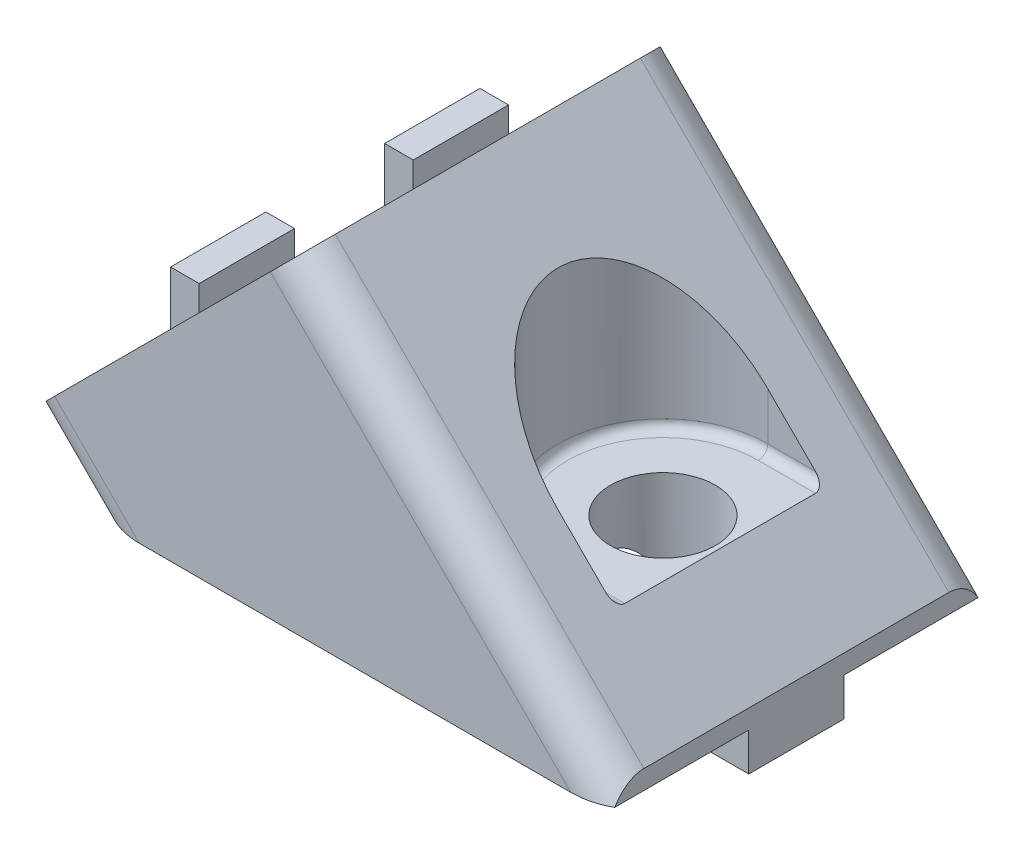
SolidWorks part; units mm, degrees
ref_plane "Front Plane" through (0, 0, 0) normal (0, 0, 1) x (1, 0, 0)
ref_plane "Top Plane" through (0, 0, 0) normal (0, 1, 0) x (1, 0, 0)
ref_plane "Right Plane" through (0, 0, 0) normal (1, 0, 0) x (0, 0, -1)
sketch "Sketch1" plane through (0, 0, 0) normal (0, 0, 1) x (1, 0, 0)
  line L0 (0, 0) -> (-3.0406, 3.0406)
  line L1 (27.2843, 1) -> (11.1016, 17.1827)
  line L2 (27.2843, 0) -> (27.2843, 1)
  line L3 (27.2843, 1) -> (28.2843, 0) construction
  line L4 (11.1016, 17.1827) -> (-3.0406, 3.0406)
  line L5 (27.2843, 0) -> (0, 0)
  line L6 (27.2843, 0) -> (28.2843, 0) construction
  dimension "D1" = 45
  dimension "D2" = 20
  dimension "D3" = 24.3
  dimension "D4" = 1
extrude "Boss-Extrude1" add sketch "Sketch1" along normal mid plane 20
sketch "Sketch2" plane through (0, 0, 0) normal (0, 1, 0) x (1, 0, 0)
  line L0 (28.2843, 0) -> (20.2843, 0) construction
  line L2 (28.2843, -10) -> (28.2843, 10) construction
  circle A0 centre (20.2843, 0) radius 2.75
  circle A1 centre (20.2843, 0) radius 5.5 construction
  dimension "D2" = 5.5
  dimension "D3" = 11
  dimension "D1" = 8
extrude "Cut-Extrude1" cut sketch "Sketch2" against normal through all from offset 5
sketch "Sketch3" plane through (0, 5, 0) normal (0, -1, 0) x (1, 0, 0)
  line L0 (20.2843, -5.5) -> (28.2843, -5.5)
  line L2 (20.2843, 5.5) -> (28.2843, 5.5)
  line L3 (28.2843, 5.5) -> (28.2843, -5.5)
  arc A0 (20.2843, 5.5) -> (20.2843, -5.5) centre (20.2843, 0) ccw
  circle A1 centre (20.2843, 0) radius 5.5 construction
extrude "Cut-Extrude2" cut sketch "Sketch3" against normal through all
fillet "Fillet1" radius 2 4 edges at (-1.5203, 1.5203, -10) (-1.5203, 1.5203, 10) (19.1929, 9.0913, -10) (19.1929, 9.0913, 10)
fillet "Fillet2" radius 0.5 3 edges at (21.7843, 5, 5.5) (21.7843, 5, -5.5) (14.7843, 5, 0)
sketch "Sketch4" plane through (0, 0, 0) normal (0, 0, 1) x (1, 0, 0)
  line L0 (27.2843, 0) -> (0, 0) construction
  line L1 (7.5, 0) -> (0, 0)
  line L2 (7.5, 0) -> (7.5, -2)
  line L3 (7.5, -2) -> (0, -2)
  line L4 (0, 0) -> (0, -2)
  line L5 (11.1016, 17.1827) -> (-3.0406, 3.0406) construction
  line L6 (24.2843, 0) -> (27.2843, 0)
  line L7 (24.2843, 0) -> (24.2843, -2)
  line L8 (24.2843, -2) -> (27.2843, -2)
  line L9 (27.2843, 0) -> (27.2843, -2)
  line L10 (-3.0406, 5.869) -> (-1.5406, 5.869)
  line L11 (-3.0406, 5.869) -> (-3.0406, 3.0406)
  line L12 (-3.0406, 3.0406) -> (-1.5406, 4.5406)
  line L13 (-1.5406, 5.869) -> (-1.5406, 4.5406)
  line L14 (8.1874, 17.0969) -> (9.6874, 17.0969)
  line L15 (8.1874, 17.0969) -> (8.1874, 14.2685)
  line L16 (8.1874, 14.2685) -> (9.6874, 15.7685)
  line L17 (9.6874, 17.0969) -> (9.6874, 15.7685)
  line L18 (27.2843, 1) -> (11.1016, 17.1827) construction
  dimension "D1" = 7.5
  dimension "D2" = 3
  dimension "D3" = 2
  dimension "D4" = 2
  dimension "D5" = 1.5
  dimension "D6" = 1.5
  dimension "D7" = 2
  dimension "D8" = 2
  dimension "D9" = 2
extrude "Boss-Extrude4" add sketch "Sketch4" along normal mid plane 5
sketch "Sketch5" plane through (-3.0406, 3.0406, 0) normal (-0.7071, 0.7071, 0) x (0, 0, 1)
  line L0 (0, 0) -> (0, 10) construction
  line L1 (2.5, 0) -> (-2.5, 0) construction
  circle A0 centre (0, 10) radius 2.75
  circle A1 centre (0, 10) radius 4 construction
  dimension "D2" = 5.5
  dimension "D3" = 8
  dimension "D1" = 10
extrude "Cut-Extrude3" cut sketch "Sketch5" along normal through all from offset 5 offset against normal yes
sketch "Sketch6" plane through (0.495, -0.495, 0) normal (-0.7071, 0.7071, 0) x (0, 0, 1)
  line L0 (-4, 10) -> (-4, 6)
  line L1 (4, 10) -> (4, 6)
  line L2 (4, 6) -> (-4, 6)
  arc A0 (4, 10) -> (-4, 10) centre (0, 10) ccw
  circle A1 centre (0, 10) radius 4 construction
extrude "Cut-Extrude4" cut sketch "Sketch6" against normal through all draft 1
sketch "Sketch7" plane through (0, 0, 0) normal (0, 0, 1) x (1, 0, 0)
  line L0 (7.5, -2) -> (7.5, 0) construction
  line L1 (8.6184, 0) -> (7.5, 0)
  line L3 (8.6184, 0) -> (4.7376, 3.7477)
  line L4 (7.5, 0) -> (4.7376, 3.7477)
  line L5 (2.8284, 0) -> (25.4558, 0) construction
  line L6 (8.6184, 0) -> (4.7376, 3.7477) construction
  line L7 (4.7376, 3.7477) -> (7.566, 6.5761) construction
extrude "Cut-Extrude5" cut sketch "Sketch7" along normal up to surface and the other way up to surface up to face at (8.7661, 2.5809, 3.9359) other way up to face at (8.7661, 2.5809, -3.9359)
fillet "Fillet3" radius 0.5 3 edges at (6.1518, 5.1619, 4) (6.1518, 5.1619, -4) (10.3945, 9.4045, 0)
fillet "Fillet4" radius 2 2 edges at (6.2714, 1.6667, 3.9554) (6.2714, 1.6667, -3.9554) tangent propagation no
